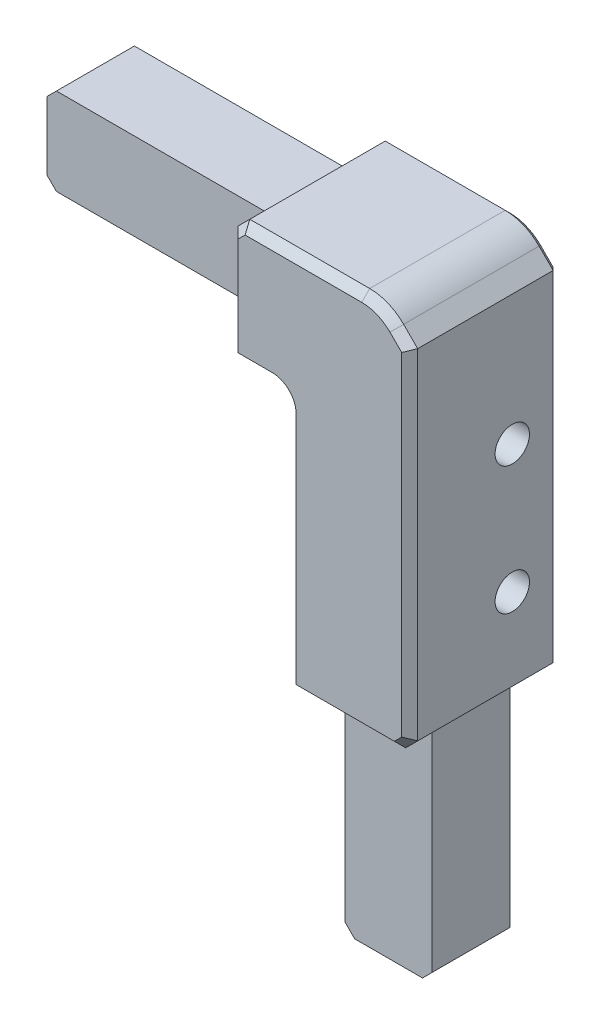
SolidWorks part; units mm, degrees
ref_plane "Front Plane" through (0, 0, 0) normal (0, 0, 1) x (1, 0, 0)
ref_plane "Top Plane" through (0, 0, 0) normal (0, 1, 0) x (1, 0, 0)
ref_plane "Right Plane" through (0, 0, 0) normal (1, 0, 0) x (0, 0, -1)
ref_plane "PZ 19.540" through (0, 0, 19.54) normal (0, 0, 1) x (1, 0, 0)
sketch "body sketch" plane through (0, 0, 19.54) normal (0, 0, 1) x (1, 0, 0)
  line L0 (4.42, 7.07) -> (-18.08, 7.07)
  line L1 (-18.08, 7.07) -> (-18.08, -8.13)
  line L2 (-18.08, -8.13) -> (-10.78, -8.13)
  line L3 (-10.78, -8.13) -> (-10.78, -40.43)
  line L4 (-10.78, -40.43) -> (4.42, -40.43)
  line L5 (4.42, -40.43) -> (4.42, 7.07)
extrude "body" add sketch "body sketch" along normal mid plane 11.42
ref_plane "PZ 20.375" through (0, 0, 20.375) normal (0, 0, 1) x (1, 0, 0)
sketch "side tongue sketch" plane through (0, 0, 20.375) normal (0, 0, 1) x (1, 0, 0)
  line L0 (-10.78, -70.43) -> (0.1, -70.43)
  line L1 (0.1, -70.43) -> (0.1, -39.43)
  line L2 (0.1, -39.43) -> (-10.78, -39.43)
  line L3 (-10.78, -39.43) -> (-10.78, -70.43)
extrude "side tongue" add sketch "side tongue sketch" along normal mid plane 9.75
sketch "end tongue sketch" plane through (0, 0, 20.375) normal (0, 0, 1) x (1, 0, 0)
  line L0 (-48.08, -8.13) -> (-17.08, -8.13)
  line L1 (-17.08, -8.13) -> (-17.08, 2.75)
  line L2 (-17.08, 2.75) -> (-48.08, 2.75)
  line L3 (-48.08, 2.75) -> (-48.08, -8.13)
extrude "end tongue" add sketch "end tongue sketch" along normal mid plane 9.75
ref_plane "PZ 23.100" through (0, 0, 23.1) normal (0, 0, 1) x (1, 0, 0)
sketch "web sketch" plane through (0, 0, 23.1) normal (0, 0, 1) x (1, 0, 0)
  line L0 (4.42, 7.07) -> (-18.08, 7.07)
  line L1 (-18.08, 7.07) -> (-18.08, 3)
  line L2 (-18.08, 3) -> (0.35, 3)
  line L3 (0.35, 3) -> (0.35, -40.43)
  line L4 (0.35, -40.43) -> (4.42, -40.43)
  line L5 (4.42, -40.43) -> (4.42, 7.07)
extrude "web" add sketch "web sketch" along normal mid plane 18.54
ref_plane "PZ 30.385" through (0, 0, 30.385) normal (0, 0, 1) x (1, 0, 0)
sketch "lip sketch" plane through (0, 0, 30.385) normal (0, 0, 1) x (1, 0, 0)
  line L0 (4.42, 7.07) -> (-18.08, 7.07)
  line L1 (-18.08, 7.07) -> (-18.08, -8.13)
  line L2 (-18.08, -8.13) -> (-10.78, -8.13)
  line L3 (-10.78, -8.13) -> (-10.78, -40.43)
  line L4 (-10.78, -40.43) -> (4.42, -40.43)
  line L5 (4.42, -40.43) -> (4.42, 7.07)
extrude "lip" add sketch "lip sketch" along normal mid plane 3.97
ref_plane "PX 0.920" through (0.92, 0, 0) normal (1, 0, 0) x (0, 0, -1)
sketch "insert holes sketch" plane through (0.92, 0, 0) normal (1, 0, 0) x (0, 0, -1)
  circle A0 centre (-19.54, -28.7) radius 2.15
  circle A1 centre (-19.54, -12.7) radius 2.15
extrude "insert holes" cut sketch "insert holes sketch" against normal mid plane 9
chamfer "bumper corner, bed side" distance 3.516 angle 45 1 edges at (4.42, 7.07, 23.1) tangent propagation no
fillet "bumper corner" radius 6 1 edges at (0.904, 7.07, 23.1) tangent propagation no
fillet "inside corner of the web" radius 1 1 edges at (0.35, 3, 26.825) tangent propagation no
fillet "reveal corner" radius 2 1 edges at (-10.78, -8.13, 30.385) tangent propagation no
fillet "body inside corner" radius 2 1 edges at (-10.78, -8.13, 19.54) tangent propagation no
chamfer "arm ends" distance 1.5 angle 45 2 edges at (-18.08, 7.07, 23.1) (4.42, -40.43, 23.1) tangent propagation no
chamfer "tongue lead-in" distance 1.2 angle 45 4 edges at (-48.08, -8.13, 20.375) (-48.08, 2.75, 20.375) (-10.78, -70.43, 20.375) (0.1, -70.43, 20.375) tangent propagation no
chamfer "front face chamfer" distance 1 angle 45 11 edges at (0.7148, 6.6133, 32.37) (3.5407, 4.4333, 32.37) (4.42, -17.688, 32.37) (3.67, -39.68, 32.37) (-3.93, -40.43, 32.37) (-10.78, -25.28, 32.37) (-11.3658, -8.7158, 32.37) (-15.43, -8.13, 32.37) (-18.08, -1.28, 32.37) (-17.33, 6.32, 32.37) (-9.0806, 7.07, 32.37)
chamfer "back face chamfer" distance 0.6 angle 45 11 edges at (-15.43, -8.13, 13.83) (-11.3658, -8.7158, 13.83) (-10.78, -25.28, 13.83) (-3.93, -40.43, 13.83) (3.67, -39.68, 13.83) (4.42, -17.688, 13.83) (3.5407, 4.4333, 13.83) (0.7148, 6.6133, 13.83) (-9.0806, 7.07, 13.83) (-17.33, 6.32, 13.83) (-18.08, -1.28, 13.83)
equation "\"diffL\"= 608.8mm"
equation "\"diffW\"= 329.4mm"
equation "\"diffT\"= 2.9mm"
equation "\"chanSlotW\"= 12.9mm"
equation "\"chanSlotDepth\"= 11.13mm"
equation "\"chanFloor\"= 1.57mm"
equation "\"chanLeg\"= 12.7mm"
equation "\"lightL\"= 605mm"
equation "\"lightW\"= 331mm"
equation "\"lightH\"= 92mm"
equation "\"lightSideFlat\"= 30mm"
equation "\"lightSlopeLen\"= 33.1mm"
equation "\"lightWingDepth\"= 47.9mm"
equation "\"lightWingFlat\"= 90.2mm"
equation "\"lightChanW\"= 99.6mm"
equation "\"lightChanStand\"= 44.1mm"
equation "\"insFlangeD\"= 12.3mm"
equation "\"insFromEnd\"= 20.7mm"
equation "\"insUpSlope\"= 20.8mm"
equation "\"gaugeH\"= 10mm"
equation "\"gaugeStepLen\"= 14mm"
equation "\"gaugeStepW0\"= 13.1mm"
equation "\"gaugeStepDW\"= 0.2mm"
equation "\"gaugeSteps\"= 5mm"
equation "\"gaugeHandleLen\"= 30mm"
equation "\"gaugeHandleW\"= 24mm"
equation "\"gaugeSlot0\"= 3mm"
equation "\"gaugeSlotD\"= 0.1mm"
equation "\"gaugeSlotDepth\"= 8mm"
equation "\"gap\"= 25.4mm"
equation "\"edgeL\"= 1mm"
equation "\"edgeW\"= 0.75mm"
equation "\"proud\"= 1.5mm"
equation "\"seatClr\"= 0.15mm"
equation "\"tongueClrZ\"= 0.1mm"
equation "\"tongueClrX\"= 0.25mm"
equation "\"tongueLen\"= 30mm"
equation "\"armSide\"= 45mm"
equation "\"armEnd\"= 20mm"
equation "\"cornerCham\"= 3mm"
equation "\"brkW\"= 26mm"
equation "\"brkT\"= 7mm"
equation "\"brkSeatClr\"= 0.2mm"
equation "\"brkScrewSpan\"= 16mm"
equation "\"pilotD\"= 2.7mm"
equation "\"pilotDepth\"= 10mm"
equation "\"screwClrD\"= 3.9mm"
equation "\"jogBelow\"= 4mm"
equation "\"padT\"= 7mm"
equation "\"padLen\"= 31mm"
equation "\"m6Clr\"= 7mm"
equation "\"m6Slot\"= 3mm"
equation "\"flangeRelD\"= 17mm"
equation "\"flangeRelDepth\"= 1.5mm"
equation "\"relLen\"= 7mm"
equation "\"relDepth\"= 4mm"
equation "\"relLand\"= 2mm"
equation "\"knockN\"= 100mm"
equation "\"petgcfE\"= 3000mm"
equation "\"mockExtent\"= 110mm"
equation "\"relZnear\"= 9.4mm"
equation "\"relZfar\"= 23.4mm"
equation "\"headD\"= 8mm"
equation "\"headH\"= 2.5mm"
equation "\"headFromEnd\"= 6.8mm"
equation "\"headBack\"= 16.4mm"
equation "\"sideClr\"= 0.4mm"
equation "\"cornerRelR\"= 1.5mm"
equation "\"cornerRelBack\"= 0.6mm"
equation "\"endHeadH\"= 2.8mm"
equation "\"footClr\"= 1.2mm"
equation "\"footEndClr\"= 3.5mm"
equation "\"footLift\"= 6mm"
equation "\"footBlockClr\"= 0.5mm"
equation "\"footBack\"= 50mm"
equation "\"footFwd\"= 10mm"
equation "\"footBraceEnd\"= 3mm"
equation "\"footLoadN\"= 25mm"
equation "\"spacerLen\"= 60mm"
equation "\"spacerShort\"= 0.5mm"
equation "\"spacerCham\"= 0.8mm"
equation "\"spacerPerSide\"= 3mm"
equation "\"spacerPerEnd\"= 1mm"
equation "\"toolR\"= 9mm"
equation "\"visR\"= 4mm"
equation "\"edgeR\"= 1mm"
equation "\"bendOutR\"= 5mm"
equation "\"insideR\"= 2.5mm"
equation "\"footCornerR\"= 10mm"
equation "\"footFrontR\"= 8mm"
equation "\"braceKinkR\"= 12mm"
equation "\"bedCham\"= 1mm"
equation "\"bedChamSmall\"= 0.6mm"
equation "\"soleTopR\"= 2mm"
equation "\"cornerR\"= 6mm"
equation "\"rimInR\"= 1mm"
equation "\"insFlangeH\"= 1mm"
equation "\"insHoleFinishD\"= 4.5mm"
equation "\"insLen\"= 6.4mm"
equation "\"footToeTip\" = 4mm"
equation "\"cgInset\" = 4mm"
equation "\"lampWeightN\" = 51mm"
equation "\"frameWeightN\" = 10mm"
equation "\"bumpIn\" = 8mm"
equation "\"bumpH\" = 3mm"
equation "\"legBelowFront\" = 2mm"
equation "\"lipClr\" = 0.1mm"
equation "\"revealR\" = 2mm"
equation "\"frontCham\" = 1mm"
